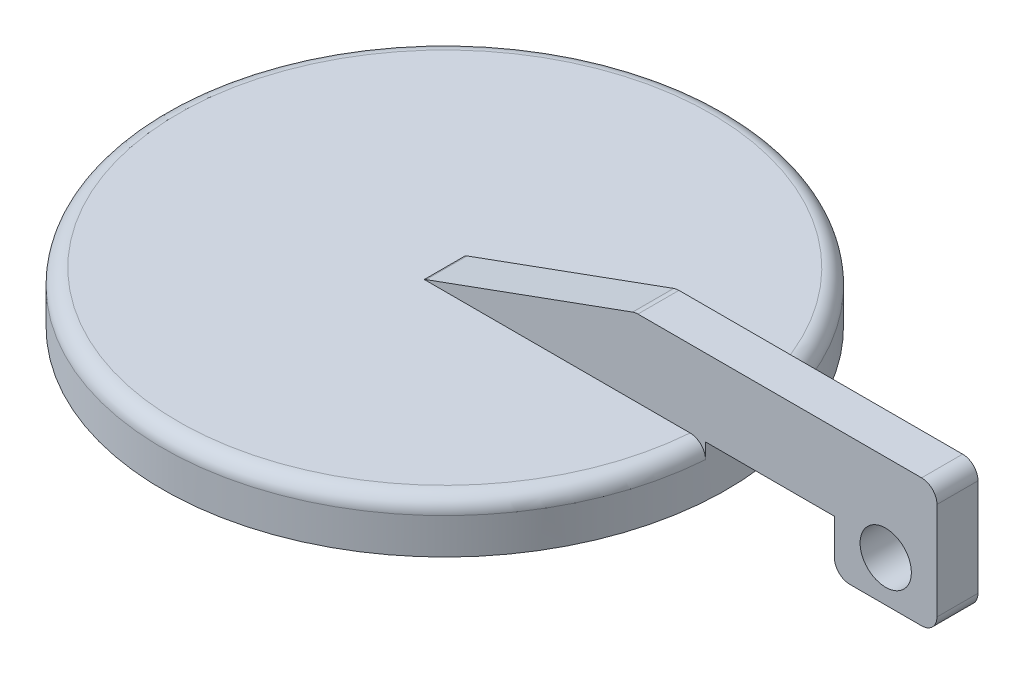
SolidWorks part; units mm, degrees
ref_plane "Front Plane" through (0, 0, 0) normal (0, 0, 1) x (1, 0, 0)
ref_plane "Top Plane" through (0, 0, 0) normal (0, 1, 0) x (1, 0, 0)
ref_plane "Right Plane" through (0, 0, 0) normal (1, 0, 0) x (0, 0, -1)
sketch "Sketch2" plane through (0, 0, 0) normal (0, 0, 1) x (1, 0, 0)
  line L7 (0, 0) -> (27.5, 0)
  line L8 (0, 0) -> (0, 5)
  line L9 (0, 5) -> (27.5, 5)
  line L10 (27.5, 0) -> (27.5, 5)
  dimension "D1" = 5
  dimension "D2" = 27.5
revolve "Revolve1" add sketch "Sketch2" angle 360 about L8
sketch "Sketch3" plane through (0, 5, 0) normal (0, 1, 0) x (1, 0, 0)
  line L0 (0, -10) -> (0, 10) construction
  line L1 (0, 10) -> (35, 10)
  line L2 (35, 10) -> (35, 6)
  line L3 (35, 6) -> (0, 6)
  line L4 (0, 10) -> (0, 6)
  line L5 (0, -10) -> (35, -10)
  line L6 (35, -10) -> (35, -6)
  line L7 (35, -6) -> (0, -6)
  line L8 (0, -6) -> (0, -10)
  line L9 (0, 2) -> (0, -2)
  line L10 (0, 2) -> (50, 2)
  line L11 (0, -2) -> (50, -2)
  line L12 (50, -2) -> (50, 2)
  point P4 (0, 0)
  point P13 (0, 0)
  circle M1 centre (0, 0) radius 27.5
  dimension "D1" = 20
  dimension "D2" = 35
  dimension "D3" = 4
  dimension "D4" = 4
  dimension "D5" = 50
extrude "Boss-Extrude1" add sketch "Sketch3" along normal blind 7.5 contours L9 L11 L10 M1 | L11 L12 L10 M1 region at (13.7379, 5, 0) region at (38.7379, 5, 0)
sketch "Sketch4" plane through (0, 0, 0) normal (0, 0, 1) x (1, 0, 0)
  line L5 (35, 8.75) -> (31.5, 8.75) construction
  line L7 (50, 8.75) -> (31.5, 8.75) construction
  line L8 (50, 12.5) -> (50, 5) construction
  line L10 (-0.0364, 5) -> (20.5697, 12.5)
  line L11 (27.4272, 5) -> (-27.5, 5) construction
  line L12 (0, 12.5) -> (50, 12.5) construction
  line L13 (0, 5) -> (27.4272, 5) construction
  line L14 (20.5697, 12.5) -> (0, 12.5)
  line L15 (0, 12.5) -> (-0.0364, 5)
  circle A0 centre (31.5, 8.75) radius 2
  dimension "D3" = 4
  dimension "D1" = 20
  dimension "D2" = 18.5
extrude "Cut-Extrude1" cut sketch "Sketch4" against normal mid plane 30 contours L14 L15 L10
sketch "Sketch6" plane through (0, 5, 0) normal (0, -1, 0) x (1, 0, 0)
  line L6 (50, 2) -> (40, 2)
  line L7 (50, 2) -> (50, -2) construction
  line L8 (27.4272, 2) -> (50, 2) construction
  line L9 (40, 2) -> (40, -2)
  line L10 (27.4272, -2) -> (50, -2) construction
  line L11 (40, -2) -> (50, -2)
  line L12 (50, -2) -> (50, 2)
  dimension "D1" = 10
extrude "Boss-Extrude2" add sketch "Sketch6" along normal blind 5
sketch "Sketch7" plane through (0, 0, 2) normal (0, 0, 1) x (1, 0, 0)
  line L0 (45, 4) -> (45, 0) construction
  line L2 (50, 0) -> (40, 0) construction
  circle A0 centre (45, 4) radius 2.5
  dimension "D2" = 5
  dimension "D1" = 4
extrude "Cut-Extrude2" cut sketch "Sketch7" against normal blind 10
fillet "Fillet2" radius 1.5 6 edges at (40, 0, 0) (50, 0, 0) (50, 12.5, 0) (20.5697, 12.5, 0) (0, 5.0133, 0) (-27.5, 5, 0)
